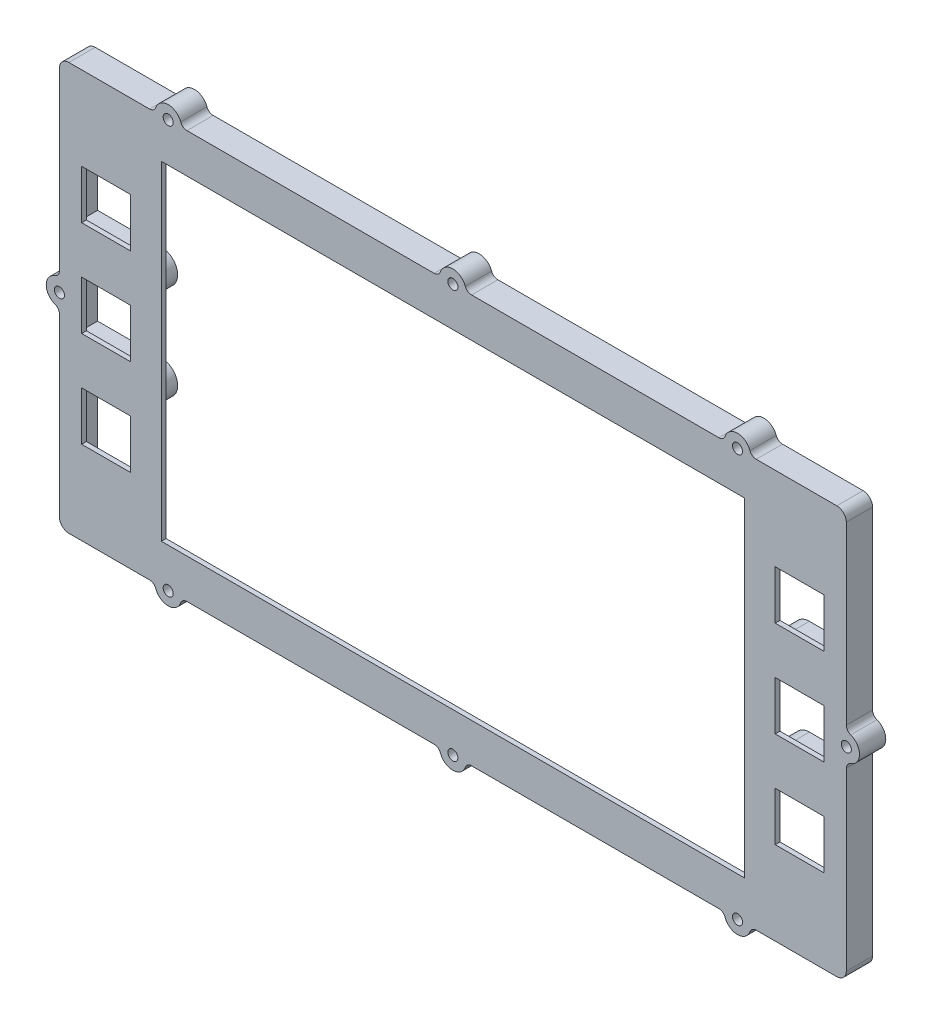
SolidWorks part; units mm, degrees
ref_plane "Front Plane" through (0, 0, 0) normal (0, 0, 1) x (1, 0, 0)
ref_plane "Top Plane" through (0, 0, 0) normal (0, 1, 0) x (1, 0, 0)
ref_plane "Right Plane" through (0, 0, 0) normal (1, 0, 0) x (0, 0, -1)
sketch "PCB" plane through (0, 0, 0) normal (0, 0, 1) x (1, 0, 0)
  line L0 (96.2635, 45.5524) -> (101.8921, 45.5524) construction
  line L1 (-101.8921, 51.181) -> (101.8921, 51.181) construction
  line L2 (-101.8921, 51.181) -> (-101.8921, -51.181) construction
  line L3 (-101.8921, -51.181) -> (101.8921, -51.181) construction
  line L4 (101.8921, 51.181) -> (101.8921, -51.181) construction
  line L5 (-101.8921, 51.181) -> (101.8921, -51.181) construction
  line L6 (-101.8921, -51.181) -> (101.8921, 51.181) construction
  line L7 (96.2635, 45.5524) -> (96.2635, 51.181) construction
  line L8 (-96.2635, 45.5524) -> (-101.8921, 45.5524) construction
  line L9 (-96.2635, -45.5524) -> (-96.2635, -51.181) construction
  line L10 (-92.8243, 0) -> (-92.8243, 25.6794) construction
  line L11 (-98.8568, 31.7119) -> (-86.7918, 31.7119)
  line L12 (-98.8568, 31.7119) -> (-98.8568, 19.6469)
  line L13 (-98.8568, 19.6469) -> (-86.7918, 19.6469)
  line L14 (-86.7918, 31.7119) -> (-86.7918, 19.6469)
  line L15 (-98.8568, 31.7119) -> (-86.7918, 19.6469) construction
  line L16 (-98.8568, 19.6469) -> (-86.7918, 31.7119) construction
  line L17 (-98.8568, 6.0325) -> (-86.7918, 6.0325)
  line L18 (-98.8568, 6.0325) -> (-98.8568, -6.0325)
  line L19 (-98.8568, -6.0325) -> (-86.7918, -6.0325)
  line L20 (-86.7918, 6.0325) -> (-86.7918, -6.0325)
  line L21 (-98.8568, 6.0325) -> (-86.7918, -6.0325) construction
  line L22 (-98.8568, -6.0325) -> (-86.7918, 6.0325) construction
  line L23 (-98.8568, -19.6469) -> (-86.7918, -19.6469)
  line L24 (-98.8568, -19.6469) -> (-98.8568, -31.7119)
  line L25 (-98.8568, -31.7119) -> (-86.7918, -31.7119)
  line L26 (-86.7918, -19.6469) -> (-86.7918, -31.7119)
  line L27 (-98.8568, -19.6469) -> (-86.7918, -31.7119) construction
  line L28 (-98.8568, -31.7119) -> (-86.7918, -19.6469) construction
  line L29 (86.7918, 31.7119) -> (98.8568, 31.7119)
  line L30 (86.7918, 31.7119) -> (86.7918, 19.6469)
  line L31 (86.7918, 19.6469) -> (98.8568, 19.6469)
  line L32 (98.8568, 31.7119) -> (98.8568, 19.6469)
  line L33 (86.7918, 31.7119) -> (98.8568, 19.6469) construction
  line L34 (86.7918, 19.6469) -> (98.8568, 31.7119) construction
  line L35 (86.7918, 6.0325) -> (98.8568, 6.0325)
  line L36 (86.7918, 6.0325) -> (86.7918, -6.0325)
  line L37 (86.7918, -6.0325) -> (98.8568, -6.0325)
  line L38 (98.8568, 6.0325) -> (98.8568, -6.0325)
  line L39 (86.7918, 6.0325) -> (98.8568, -6.0325) construction
  line L40 (86.7918, -6.0325) -> (98.8568, 6.0325) construction
  line L41 (86.7918, -19.6469) -> (98.8568, -19.6469)
  line L42 (86.7918, -19.6469) -> (86.7918, -31.7119)
  line L43 (86.7918, -31.7119) -> (98.8568, -31.7119)
  line L44 (98.8568, -19.6469) -> (98.8568, -31.7119)
  line L45 (86.7918, -19.6469) -> (98.8568, -31.7119) construction
  line L46 (86.7918, -31.7119) -> (98.8568, -19.6469) construction
  line L47 (-92.8243, 0) -> (-92.8243, -25.6794) construction
  line L48 (-92.8243, 25.6794) -> (-101.8921, 25.6794) construction
  line L49 (92.8243, 25.6794) -> (101.8921, 25.6794) construction
  circle A0 centre (-96.2635, 45.5524) radius 0.9995
  circle A1 centre (-96.2635, -45.5524) radius 0.9995
  circle A2 centre (96.2635, -45.5524) radius 0.9995
  circle A3 centre (96.2635, 45.5524) radius 0.9995
  point P0 (0, 0)
  point P14 (-92.8243, 25.6794)
  point P23 (-92.8243, 0)
  point P28 (-92.8243, -25.6794)
  point P33 (92.8243, 25.6794)
  point P38 (92.8243, 0)
  point P43 (92.8243, -25.6794)
  dimension "D4" = 1.999
  dimension "D1" = 203.7842
  dimension "D2" = 102.362
  dimension "D3" = 5.6286
  dimension "D5" = 25.5016
  dimension "D6" = 25.5016
  dimension "D7" = 9.0678
  dimension "D8" = 12.065
sketch "display_screen" plane through (0, 0, 0) normal (0, 0, 1) x (1, 0, 0)
  line L1 (-80.3275, 46.3296) -> (83.7565, 46.3296) construction
  line L2 (-80.3275, 46.3296) -> (-80.3275, -50.9016) construction
  line L3 (-80.3275, -50.9016) -> (83.7565, -50.9016) construction
  line L4 (83.7565, 46.3296) -> (83.7565, -50.9016) construction
  line L5 (-78.2955, 44.2976) -> (78.2955, 44.2976) construction
  line L6 (-78.2955, 44.2976) -> (-78.2955, -44.2976) construction
  line L7 (-78.2955, -44.2976) -> (78.2955, -44.2976) construction
  line L8 (78.2955, 44.2976) -> (78.2955, -44.2976) construction
  point P8 (0, 44.2976)
  point P10 (-78.2955, 0)
  dimension "D1" = 164.084
  dimension "D2" = 97.2312
  dimension "D3" = 6.604
  dimension "D4" = 2.032
  dimension "D5" = 2.032
  dimension "D6" = 5.461
ref_plane "foam_thickness" through (0, 0, 2.9972) normal (0, 0, 1) x (1, 0, 0)
ref_plane "face_of_screen" through (0, 0, 5.7658) normal (0, 0, 1) x (1, 0, 0)
sketch "Sketch1" plane through (0, 0, 0) normal (0, 0, 1) x (1, 0, 0)
  line L0 (-101.8921, 51.181) -> (101.8921, 51.181) construction
  line L1 (-105.3211, 54.5846) -> (105.3211, 54.5846)
  line L2 (-105.3211, 54.5846) -> (-105.3211, -54.5846)
  line L3 (-105.3211, -54.5846) -> (105.3211, -54.5846)
  line L4 (105.3211, 54.5846) -> (105.3211, -54.5846)
  line L5 (45.6565, 49.7078) -> (45.6565, 51.4096)
  line L6 (-80.3275, 46.3296) -> (-80.3275, -50.9016) construction
  line L7 (45.6565, 51.4096) -> (-42.2275, 51.4096)
  line L8 (83.7565, 46.3296) -> (83.7565, -50.9016) construction
  line L9 (-102.1461, 51.4096) -> (-102.1461, 54.5846) construction
  line L10 (-102.1461, 51.4096) -> (-105.3211, 51.4096) construction
  line L11 (102.1461, -51.4096) -> (105.3211, -51.4096) construction
  line L12 (102.1461, -51.4096) -> (102.1461, -54.5846) construction
  line L13 (101.8921, 51.181) -> (101.8921, -51.181) construction
  line L14 (-80.3275, 49.7078) -> (-80.3275, 51.4096)
  line L15 (-80.3275, 51.4096) -> (-102.1461, 51.4096)
  line L16 (-102.1461, 51.4096) -> (-102.1461, 17.1069)
  line L17 (-101.8921, 51.181) -> (-101.8921, -51.181) construction
  line L18 (-102.1461, 17.1069) -> (-84.9757, 17.1069)
  line L19 (-42.2275, 51.4096) -> (-42.2275, 49.7078)
  line L20 (77.4065, 49.7078) -> (77.4065, 51.4096)
  line L21 (-84.9757, 8.5725) -> (-102.1461, 8.5725)
  line L22 (-102.1461, 8.5725) -> (-102.1461, -8.5725)
  line L23 (-102.1461, -8.5725) -> (-84.9757, -8.5725)
  line L24 (77.4065, 51.4096) -> (52.0065, 51.4096)
  line L25 (-84.9757, -17.1069) -> (-102.1461, -17.1069)
  line L26 (-102.1461, -17.1069) -> (-102.1461, -51.4096)
  line L27 (52.0065, 49.7078) -> (52.0065, 51.4096)
  line L28 (-80.3275, -50.9016) -> (83.7565, -50.9016) construction
  line L29 (-101.8921, -51.181) -> (101.8921, -51.181) construction
  line L30 (-48.5775, 49.7078) -> (-48.5775, 51.4096)
  line L31 (-98.8568, 19.6469) -> (-86.7918, 19.6469) construction
  line L32 (-98.8568, 6.0325) -> (-86.7918, 6.0325) construction
  line L33 (-98.8568, -6.0325) -> (-86.7918, -6.0325) construction
  line L34 (-48.5775, 51.4096) -> (-73.9775, 51.4096)
  line L35 (-98.8568, -19.6469) -> (-86.7918, -19.6469) construction
  line L36 (-73.9775, 49.7078) -> (-73.9775, 51.4096)
  line L38 (83.7565, 49.7078) -> (83.7565, 51.4096)
  line L39 (83.7565, 51.4096) -> (102.1461, 51.4096)
  line L40 (102.1461, 51.4096) -> (102.1461, 17.1069)
  line L41 (-80.3275, 46.3296) -> (83.7565, 46.3296) construction
  line L42 (102.1461, 17.1069) -> (88.4047, 17.1069)
  line L43 (88.4047, 8.5725) -> (102.1461, 8.5725)
  line L44 (102.1461, 8.5725) -> (102.1461, -8.5725)
  line L45 (102.1461, -8.5725) -> (88.4047, -8.5725)
  line L46 (88.4047, -17.1069) -> (102.1461, -17.1069)
  line L47 (102.1461, -17.1069) -> (102.1461, -51.4096)
  line L48 (102.1461, -51.4096) -> (81.9389, -51.4096)
  line L49 (83.7565, 51.4096) -> (77.4065, 51.4096) construction
  line L50 (52.0065, 51.4096) -> (45.6565, 51.4096) construction
  line L51 (-80.3275, 51.4096) -> (-73.9775, 51.4096) construction
  line L52 (-48.5775, 51.4096) -> (-42.2275, 51.4096) construction
  line L53 (-78.5099, -51.4096) -> (-102.1461, -51.4096)
  line L54 (-46.7599, -51.4096) -> (-75.7951, -51.4096)
  line L55 (47.4741, -51.4096) -> (-44.0451, -51.4096)
  line L56 (79.2241, -51.4096) -> (50.1889, -51.4096)
  arc A0 (88.4047, -8.5725) -> (88.4047, -17.1069) centre (88.4047, -12.8397) ccw
  arc A1 (88.4047, 17.1069) -> (88.4047, 8.5725) centre (88.4047, 12.8397) ccw
  arc A2 (-84.9757, -17.1069) -> (-84.9757, -8.5725) centre (-84.9757, -12.8397) ccw
  arc A3 (-84.9757, 8.5725) -> (-84.9757, 17.1069) centre (-84.9757, 12.8397) ccw
  arc A4 (83.7565, 49.7078) -> (77.4065, 49.7078) centre (80.5815, 49.7078) cw
  arc A5 (52.0065, 49.7078) -> (45.6565, 49.7078) centre (48.8315, 49.7078) cw
  arc A6 (-80.3275, 49.7078) -> (-73.9775, 49.7078) centre (-77.1525, 49.7078) ccw
  arc A7 (-48.5775, 49.7078) -> (-42.2275, 49.7078) centre (-45.4025, 49.7078) ccw
  arc A8 (81.9389, -51.4096) -> (79.2241, -51.4096) centre (80.5815, -54.2798) ccw
  arc A9 (50.1889, -51.4096) -> (47.4741, -51.4096) centre (48.8315, -54.2798) ccw
  arc A10 (-78.5099, -51.4096) -> (-75.7951, -51.4096) centre (-77.1525, -54.2798) cw
  arc A11 (-46.7599, -51.4096) -> (-44.0451, -51.4096) centre (-45.4025, -54.2798) cw
  point P52 (84.1375, 12.8397)
  point P61 (-80.7085, 12.8397)
  point P72 (80.5815, 46.5328)
  point P80 (80.5815, -51.1048)
  point P92 (48.8315, -51.1048)
  point P93 (-77.1525, -51.1048)
  point P94 (-45.4025, -51.1048)
  dimension "D2" = 2.54
  dimension "D3" = 2.54
  dimension "D4" = 2.54
  dimension "D5" = 2.54
  dimension "D6" = 0.2286
  dimension "D7" = 0.254
  dimension "D8" = 0.2286
  dimension "D9" = 0.254
  dimension "D10" = 0.381
  dimension "D11" = 0.381
  dimension "D12" = 0.2032
  dimension "D13" = 6.35
  dimension "D14" = 25.4
  dimension "D15" = 0.2032
  dimension "D16" = 3.175
extrude "Boss-Extrude1" add sketch "Sketch1" along normal up to surface (5.7658 mm away) up to plane "face_of_screen"
sketch "Sketch2" plane through (0, 0, 5.7658) normal (0, 0, 1) x (1, 0, 0)
  line L0 (-78.0415, 44.0436) -> (-78.0415, 44.2976) construction
  line L1 (-105.3211, 54.5846) -> (105.3211, 54.5846)
  line L2 (-105.3211, 54.5846) -> (-105.3211, -54.5846)
  line L3 (-105.3211, -54.5846) -> (105.3211, -54.5846)
  line L4 (105.3211, 54.5846) -> (105.3211, -54.5846)
  line L5 (86.7918, 19.6469) -> (98.8568, 31.7119) construction
  line L6 (99.3648, 32.2199) -> (86.2838, 32.2199)
  line L7 (99.3648, 32.2199) -> (99.3648, 19.1389)
  line L8 (99.3648, 19.1389) -> (86.2838, 19.1389)
  line L9 (86.2838, 32.2199) -> (86.2838, 19.1389)
  line L10 (99.3648, 32.2199) -> (86.2838, 19.1389) construction
  line L11 (99.3648, 19.1389) -> (86.2838, 32.2199) construction
  line L12 (86.7918, 31.7119) -> (98.8568, 31.7119) construction
  line L13 (99.3648, 6.5405) -> (86.2838, 6.5405)
  line L14 (99.3648, 6.5405) -> (99.3648, -6.5405)
  line L15 (99.3648, -6.5405) -> (86.2838, -6.5405)
  line L16 (86.2838, 6.5405) -> (86.2838, -6.5405)
  line L17 (99.3648, 6.5405) -> (86.2838, -6.5405) construction
  line L18 (99.3648, -6.5405) -> (86.2838, 6.5405) construction
  line L19 (99.3648, -19.1389) -> (86.2838, -19.1389)
  line L20 (99.3648, -19.1389) -> (99.3648, -32.2199)
  line L21 (99.3648, -32.2199) -> (86.2838, -32.2199)
  line L22 (86.2838, -19.1389) -> (86.2838, -32.2199)
  line L23 (99.3648, -19.1389) -> (86.2838, -32.2199) construction
  line L24 (99.3648, -32.2199) -> (86.2838, -19.1389) construction
  line L25 (-86.2838, -19.1389) -> (-99.3648, -19.1389)
  line L26 (-86.2838, -19.1389) -> (-86.2838, -32.2199)
  line L27 (-86.2838, -32.2199) -> (-99.3648, -32.2199)
  line L28 (-99.3648, -19.1389) -> (-99.3648, -32.2199)
  line L29 (-78.0415, 44.0436) -> (78.0415, 44.0436)
  line L30 (-78.0415, 44.0436) -> (-78.0415, -44.0436)
  line L31 (-78.0415, -44.0436) -> (78.0415, -44.0436)
  line L32 (78.0415, 44.0436) -> (78.0415, -44.0436)
  line L33 (-78.2955, 44.2976) -> (78.2955, 44.2976) construction
  line L34 (-78.0415, 44.0436) -> (-78.2955, 44.0436) construction
  line L35 (-78.2955, 44.2976) -> (-78.2955, -44.2976) construction
  line L36 (78.0415, -44.0436) -> (78.2955, -44.0436) construction
  line L37 (78.2955, 44.2976) -> (78.2955, -44.2976) construction
  line L38 (78.0415, -44.0436) -> (78.0415, -44.2976) construction
  line L39 (-78.2955, -44.2976) -> (78.2955, -44.2976) construction
  line L40 (-86.2838, -19.1389) -> (-99.3648, -32.2199) construction
  line L41 (-86.2838, -32.2199) -> (-99.3648, -19.1389) construction
  line L42 (-99.3648, 6.5405) -> (-86.2838, 6.5405)
  line L43 (-99.3648, 6.5405) -> (-99.3648, -6.5405)
  line L44 (-99.3648, -6.5405) -> (-86.2838, -6.5405)
  line L45 (-86.2838, 6.5405) -> (-86.2838, -6.5405)
  line L46 (-99.3648, 6.5405) -> (-86.2838, -6.5405) construction
  line L47 (-99.3648, -6.5405) -> (-86.2838, 6.5405) construction
  line L48 (-99.3648, 32.2199) -> (-86.2838, 32.2199)
  line L49 (-99.3648, 32.2199) -> (-99.3648, 19.1389)
  line L50 (-99.3648, 19.1389) -> (-86.2838, 19.1389)
  line L51 (-86.2838, 32.2199) -> (-86.2838, 19.1389)
  line L52 (-99.3648, 32.2199) -> (-86.2838, 19.1389) construction
  line L53 (-99.3648, 19.1389) -> (-86.2838, 32.2199) construction
  point P6 (92.8243, 25.6794)
  point P15 (92.8243, 0)
  point P24 (92.8243, -25.6794)
  point P31 (-92.8243, -25.6794)
  point P38 (-92.8243, 0)
  point P65 (-92.8243, 25.6794)
  dimension "D1" = 0.254
  dimension "D2" = 0.508
extrude "Boss-Extrude2" add sketch "Sketch2" along normal blind 1.27
sketch "Sketch3" plane through (0, 0, 0) normal (0, 0, 1) x (1, 0, 0)
  line L0 (105.3211, 54.5846) -> (-105.3211, 54.5846) construction
  line L1 (5.002, 54.5846) -> (5.002, 52.2986)
  line L2 (5.002, 52.2986) -> (-5.002, 52.2986)
  line L3 (-5.002, 52.2986) -> (-5.002, 54.5846)
  line L4 (0, 54.5846) -> (76.2, 54.5846) construction
  line L5 (0, 54.5846) -> (-76.2, 54.5846) construction
  line L6 (-81.202, 54.5846) -> (-81.202, 52.2986)
  line L7 (-81.202, 52.2986) -> (-71.198, 52.2986)
  line L8 (-71.198, 52.2986) -> (-71.198, 54.5846)
  line L9 (71.198, 54.5846) -> (71.198, 52.2986)
  line L10 (71.198, 52.2986) -> (81.202, 52.2986)
  line L11 (81.202, 52.2986) -> (81.202, 54.5846)
  circle A0 centre (0, 54.5846) radius 1.3462
  arc A1 (5.002, 54.5846) -> (3.3267, 55.7671) centre (5.002, 56.3626) cw
  arc A2 (3.3267, 55.7671) -> (-3.3267, 55.7671) centre (0, 54.5846) ccw
  arc A3 (-3.3267, 55.7671) -> (-5.002, 54.5846) centre (-5.002, 56.3626) cw
  circle A4 centre (76.2, 54.5846) radius 1.3462
  circle A5 centre (-76.2, 54.5846) radius 1.3462
  arc A6 (81.202, 54.5846) -> (79.5267, 55.7671) centre (81.202, 56.3626) cw
  arc A7 (79.5267, 55.7671) -> (72.8733, 55.7671) centre (76.2, 54.5846) ccw
  arc A8 (72.8733, 55.7671) -> (71.198, 54.5846) centre (71.198, 56.3626) cw
  arc A9 (-71.198, 54.5846) -> (-72.8733, 55.7671) centre (-71.198, 56.3626) cw
  arc A10 (-72.8733, 55.7671) -> (-79.5267, 55.7671) centre (-76.2, 54.5846) ccw
  arc A11 (-79.5267, 55.7671) -> (-81.202, 54.5846) centre (-81.202, 56.3626) cw
  dimension "D1" = 2.6924
  dimension "D2" = 3.5306
  dimension "D3" = 1.778
  dimension "D5" = 2.286
  dimension "D6" = 76.2
extrude "Cut-Extrude1" cut sketch "Sketch3" along normal up to next contours A0 | A4 | A5
extrude "Boss-Extrude3" add sketch "Sketch3<3>" along normal up to surface (7.0358 mm away) up to face at (92.8243, 25.6794, 7.0358)
sketch "Sketch3<3>" plane through (0, 0, 0) normal (0, 0, 1) x (1, 0, 0) same geometry as "Sketch3"
mirror "Mirror1" about plane through (0, 0, 0) normal (0, 1, 0) of "Boss-Extrude3", "Cut-Extrude1"
fillet "Fillet1" radius 2.54 4 edges at (-105.3211, -54.5846, 3.5179) (105.3211, -54.5846, 3.5179) (-105.3211, 54.5846, 3.5179) (105.3211, 54.5846, 3.5179)
sketch "Sketch4" plane through (0, 0, 0) normal (0, 0, 1) x (1, 0, 0)
  line L0 (105.3211, -52.0446) -> (105.3211, 52.0446) construction
  line L1 (105.3211, -5.002) -> (103.0351, -5.002)
  line L2 (103.0351, -5.002) -> (103.0351, 5.002)
  line L3 (103.0351, 5.002) -> (105.3211, 5.002)
  line L4 (5.002, 54.5846) -> (5.002, 52.2986) construction
  circle A0 centre (105.3211, 0) radius 1.3462
  arc A1 (105.3211, -5.002) -> (106.5036, -3.3267) centre (107.0991, -5.002) cw
  arc A2 (106.5036, -3.3267) -> (106.5036, 3.3267) centre (105.3211, 0) ccw
  arc A3 (106.5036, 3.3267) -> (105.3211, 5.002) centre (107.0991, 5.002) cw
  circle A4 centre (0, 54.5846) radius 1.3462 construction
  arc A5 (3.3267, 55.7671) -> (5.002, 54.5846) centre (5.002, 56.3626) ccw construction
  arc A6 (3.3267, 55.7671) -> (-3.3267, 55.7671) centre (0, 54.5846) ccw construction
extrude "Cut-Extrude2" cut sketch "Sketch4" along normal up to next contours A0
extrude "Boss-Extrude4" add sketch "Sketch4<3>" along normal up to surface (7.0358 mm away) up to face at (-74.8538, -54.5846, 7.0358)
sketch "Sketch4<3>" plane through (0, 0, 0) normal (0, 0, 1) x (1, 0, 0) same geometry as "Sketch4"
mirror "Mirror2" about plane through (0, 0, 0) normal (1, 0, 0) of "Boss-Extrude4", "Cut-Extrude2"
